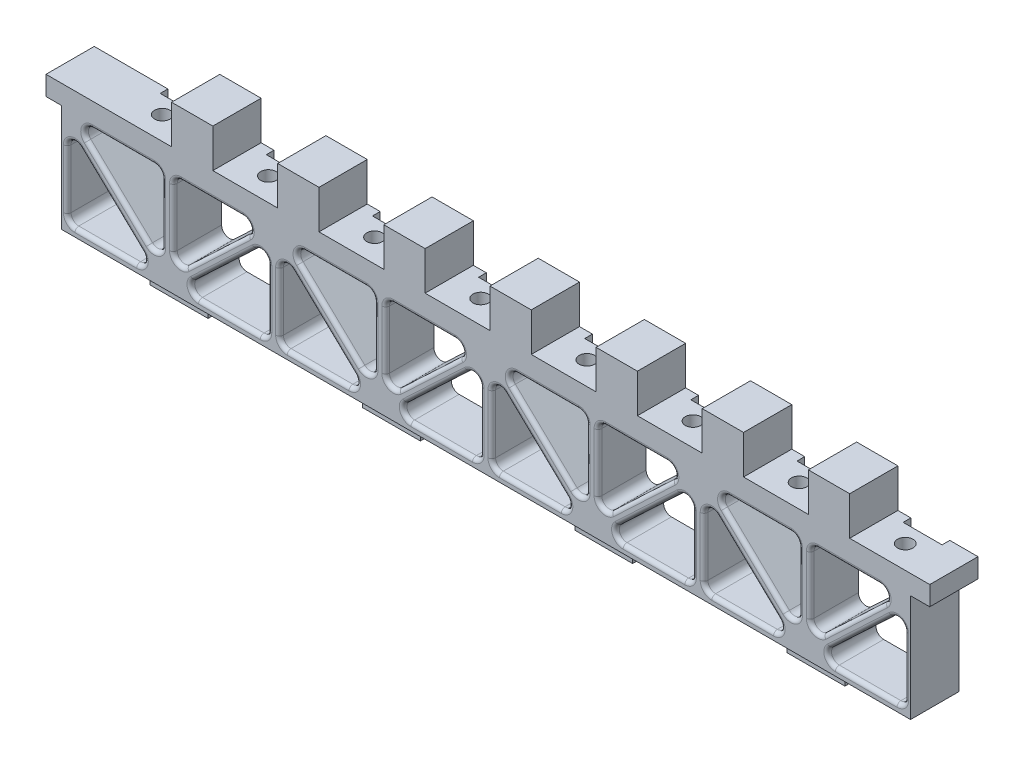
SolidWorks part; units mm, degrees
ref_plane "Front Plane" through (0, 0, 0) normal (0, 0, 1) x (1, 0, 0)
ref_plane "Top Plane" through (0, 0, 0) normal (0, 1, 0) x (1, 0, 0)
ref_plane "Right Plane" through (0, 0, 0) normal (1, 0, 0) x (0, 0, -1)
sketch "Sketch1" plane through (0, 0, 0) normal (0, 1, 0) x (1, 0, 0)
  line L1 (0, 0) -> (228.98, 0)
  line L2 (0, 0) -> (0, 12.5)
  line L3 (0, 12.5) -> (228.98, 12.5)
  line L4 (228.98, 0) -> (228.98, 12.5)
  dimension "D1" = 12.5
  dimension "D2" = 228.98
extrude "Boss-Extrude1" add sketch "Sketch1" along normal blind 5
sketch "Sketch2" plane through (0, 5, 0) normal (0, 1, 0) x (1, 0, 0)
  line L0 (228.98, 12.5) -> (0, 12.5) construction
  line L1 (19.08, 12.5) -> (29.18, 12.5)
  line L2 (19.08, 12.5) -> (19.08, 10.5)
  line L3 (19.08, 10.5) -> (29.18, 10.5)
  line L4 (29.18, 12.5) -> (29.18, 10.5)
  line L5 (0, 12.5) -> (0, 0) construction
  dimension "D1" = 19.08
  dimension "D2" = 10.1
  dimension "D3" = 2
sketch "Sketch3" plane through (0, 5, 0) normal (0, 1, 0) x (1, 0, 0)
  line L0 (0, 0) -> (228.98, 0) construction
  line L1 (19.08, 12.5) -> (19.08, 10.5) construction
  circle A0 centre (24.13, 6) radius 2
  dimension "D1" = 4
  dimension "D2" = 6
  dimension "D3" = 5.05
extrude "Cut-Extrude1" cut sketch "Sketch2" against normal blind 3.05
extrude "Cut-Extrude2" cut sketch "Sketch3" against normal blind 4
pattern_linear "LPattern1" count 8 spacing 27.5 along (1, 0, 0) of "Cut-Extrude1", "Cut-Extrude2"
sketch "Sketch4" plane through (0, 0, 0) normal (0, 0, 1) x (1, 0, 0)
  line L1 (4, 0.2046) -> (31.5, 0.2046)
  line L2 (4, 0.2046) -> (4, -27.7954)
  line L3 (4, -27.7954) -> (31.5, -27.7954)
  line L4 (31.5, 0.2046) -> (31.5, 0)
  line L5 (30, -1.2954) -> (7, -1.2954)
  line L6 (7, -1.2954) -> (30, -23.1973)
  line L7 (30, -23.1973) -> (30, -1.2954)
  line L8 (5.5, -3.8935) -> (5.5, -25.7954)
  line L9 (5.5, -25.7954) -> (28.5, -25.7954)
  line L10 (28.5, -25.7954) -> (5.5, -3.8935)
  line L11 (0, 5) -> (0, 0) construction
  line L12 (0, 0) -> (228.98, 0) construction
  line L13 (31.5, -27.7954) -> (59, -27.7954)
  line L15 (31.5, 0) -> (59, 0)
  line L16 (59, -27.7954) -> (59, 0)
  line L17 (33, -1.5) -> (33, -23.1973)
  line L18 (33, -23.1973) -> (56, -1.5)
  line L19 (56, -1.5) -> (33, -1.5)
  line L20 (34.5, -25.7954) -> (57.5, -25.7954)
  line L21 (57.5, -25.7954) -> (57.5, -4.0981)
  line L22 (57.5, -4.0981) -> (34.5, -25.7954)
  dimension "D1" = 28
  dimension "D2" = 27.5
  dimension "D3" = 1.5
  dimension "D4" = 1.5
  dimension "D5" = 2
  dimension "D6" = 1.5
  dimension "D7" = 3
  dimension "D8" = 3
  dimension "D9" = 4
  dimension "D10" = 27.5
  dimension "D11" = 1.5
  dimension "D12" = 1.5
  dimension "D13" = 1.5
  dimension "D14" = 3
  dimension "D15" = 3
  dimension "D16" = 1.5
  dimension "D17" = 1.5
  dimension "D18" = 1.5
  dimension "D19" = 1.5
extrude "Boss-Extrude2" add sketch "Sketch4" against normal blind 12.5
fillet "Fillet1" radius 2 12 edges at (57.5, -25.7954, -6.25) (57.5, -4.0981, -6.25) (30, -1.2954, -6.25) (33, -1.5, -6.25) (56, -1.5, -6.25) (5.5, -25.7954, -6.25) (5.5, -3.8935, -6.25) (7, -1.2954, -6.25) (34.5, -25.7954, -6.25) (28.5, -25.7954, -6.25) (30, -23.1973, -6.25) (33, -23.1973, -6.25)
fillet "Fillet2" radius 1 24 edges at (25.3565, -24.5381, 0) (15.4998, -25.7954, 0) (6.0858, -25.2096, 0) (5.5, -16.1776, 0) (6.7121, -6.7215, 0) (56.2922, -6.8979, 0) (57.5, -16.2649, 0) (56.9142, -25.2096, 0) (47.5173, -25.7954, 0) (37.6759, -24.5338, 0) (34.2078, -20.3975, 0) (33, -11.0306, 0) (33.5858, -2.0858, 0) (42.9827, -1.5, 0) (52.8241, -2.7616, 0) (28.7879, -20.3693, 0) (18.621, -12.3616, 0) (10.1435, -2.5527, 0) (20.0002, -1.2954, 0) (29.4142, -1.8812, 0) (16.879, -14.7292, 0) (46.1449, -14.81, 0) (44.3551, -12.4854, 0) (30, -10.9132, 0)
sketch "Sketch5" plane through (0, -27.7954, 0) normal (0, -1, 0) x (1, 0, 0)
  line L0 (4, 0) -> (59, 0) construction
  line L1 (24, -3) -> (39, -3)
  line L2 (24, -3) -> (24, -9.5)
  line L3 (24, -9.5) -> (39, -9.5)
  line L4 (39, -3) -> (39, -9.5)
  line L8 (4, 0) -> (4, -12.5) construction
  dimension "D1" = 6.5
  dimension "D2" = 3
  dimension "D3" = 15
  dimension "D4" = 20
extrude "Boss-Extrude3" add sketch "Sketch5" along normal blind 4
pattern_linear "LPattern2" count 4 spacing 55 along (1, 0, 0) of "Boss-Extrude2", "Fillet1", "Fillet2", "Boss-Extrude3"
sketch "Sketch6" plane through (0, 5, 0) normal (0, 1, 0) x (1, 0, 0)
  line L0 (46.58, 12.5) -> (29.18, 12.5) construction
  line L1 (32.53, 12.5) -> (43.23, 12.5)
  line L2 (32.53, 12.5) -> (32.53, 0)
  line L3 (32.53, 0) -> (43.23, 0)
  line L4 (43.23, 12.5) -> (43.23, 0)
  line L5 (0, 0) -> (228.98, 0) construction
  line L6 (29.18, 10.5) -> (29.18, 12.5) construction
  line L7 (46.58, 12.5) -> (46.58, 10.5) construction
  dimension "D1" = 3.35
  dimension "D2" = 3.35
extrude "Boss-Extrude4" add sketch "Sketch6" along normal blind 10
pattern_linear "LPattern3" count 7 spacing 27.5 along (1, 0, 0) of "Boss-Extrude4"
